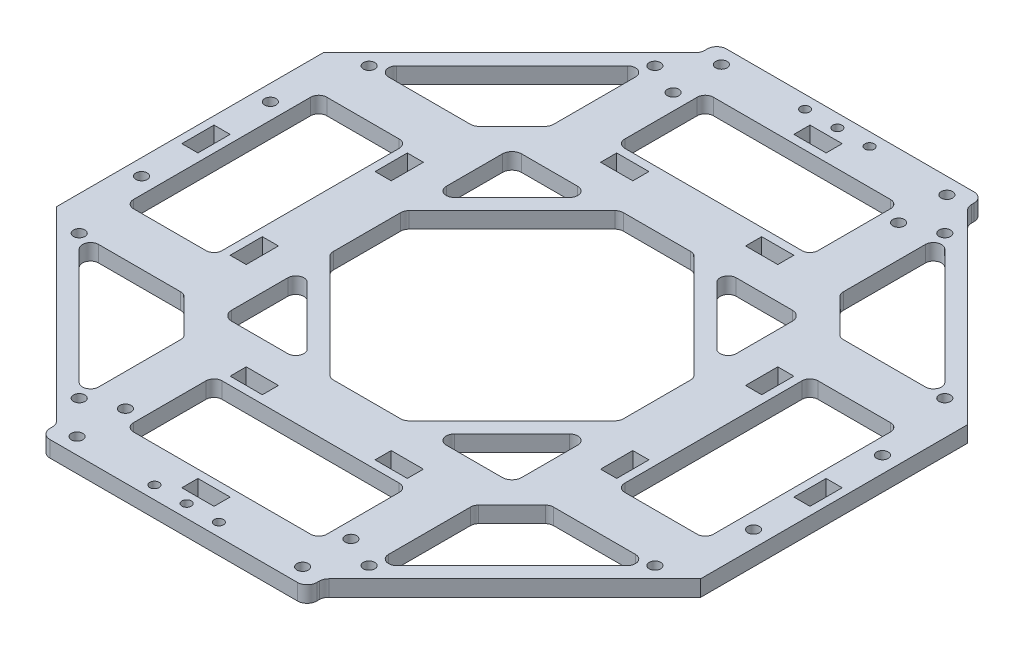
SolidWorks part; units mm, degrees
material "Custom Plastic"
ref_plane "Front Plane" through (0, 0, 0) normal (0, 0, 1) x (1, 0, 0)
ref_plane "Top Plane" through (0, 0, 0) normal (0, 1, 0) x (1, 0, 0)
ref_plane "Right Plane" through (0, 0, 0) normal (1, 0, 0) x (0, 0, -1)
ref_axis "Axis1" through (0, -18.6023, 0) along (0, 1, 0)
sketch "Base sketch" plane through (0, 0, 0) normal (0, 1, 0) x (1, 0, 0)
  line L1 (-127, 52.6051) -> (-127, -52.6051)
  line L2 (-127, -52.6051) -> (-52.6051, -127)
  line L3 (-52.6051, -127) -> (52.6051, -127)
  line L4 (52.6051, -127) -> (127, -52.6051)
  line L5 (127, -52.6051) -> (127, 52.6051)
  line L6 (127, 52.6051) -> (52.6051, 127)
  line L7 (52.6051, 127) -> (-52.6051, 127)
  line L8 (-52.6051, 127) -> (-127, 52.6051)
  circle A0 centre (0, 0) radius 127 construction
  dimension "D1" = 254
extrude "Base" add sketch "Base sketch" along normal blind 6.35
sketch "Sketch3" plane through (0, 6.35, 0) normal (0, 1, 0) x (1, 0, 0)
  line L0 (52.6051, 127) -> (-52.6051, 127) construction
  line L1 (-38.1, 114.3) -> (38.1, 114.3)
  line L2 (-38.1, 114.3) -> (-38.1, 79.375)
  line L4 (-38.1, 79.375) -> (38.1, 79.375)
  line L5 (38.1, 114.3) -> (38.1, 79.375)
  point P6 (0, 79.375)
  dimension "D1" = 76.2
  dimension "D2" = 34.925
  dimension "D3" = 12.7
extrude "Wheel cutout" cut sketch "Sketch3" against normal up to next
fillet "Wheel cutout fillets" radius 3.175 4 edges at (38.1, 3.175, -114.3) (38.1, 3.175, -79.375) (-38.1, 3.175, -79.375) (-38.1, 3.175, -114.3)
pattern_circular "Wheel cutout pattern" count 4 over 360 about axis through (0, -18.6023, 0) along (0, 1, 0) of "Wheel cutout", "Wheel cutout fillets"
sketch "Sketch4" plane through (0, 6.35, 0) normal (0, 1, 0) x (1, 0, 0)
  line L0 (0, 0) -> (0, 127) construction
  line L1 (52.6051, 127) -> (-52.6051, 127) construction
  line L2 (34.925, 120.65) -> (-34.925, 120.65) construction
  line L3 (-34.925, 123.825) -> (-22.225, 123.825) construction
  line L4 (-34.925, 123.825) -> (-34.925, 117.475) construction
  line L5 (-34.925, 117.475) -> (-22.225, 117.475) construction
  line L6 (-22.225, 123.825) -> (-22.225, 117.475) construction
  line L7 (-34.925, 123.825) -> (-22.225, 117.475) construction
  line L8 (-34.925, 117.475) -> (-22.225, 123.825) construction
  line L9 (34.925, 114.3) -> (-34.925, 114.3) construction
  line L10 (34.925, 117.475) -> (22.225, 123.825) construction
  line L11 (34.925, 123.825) -> (22.225, 117.475) construction
  line L12 (22.225, 123.825) -> (22.225, 117.475) construction
  line L13 (34.925, 117.475) -> (22.225, 117.475) construction
  line L14 (34.925, 123.825) -> (34.925, 117.475) construction
  line L15 (34.925, 123.825) -> (22.225, 123.825) construction
  line L16 (-38.1, 96.8375) -> (38.1, 96.8375) construction
  line L17 (-38.1, 111.125) -> (-38.1, 82.55) construction
  line L18 (38.1, 82.55) -> (38.1, 111.125) construction
  line L19 (34.925, 69.85) -> (22.225, 76.2) construction
  line L20 (34.925, 76.2) -> (22.225, 69.85) construction
  line L21 (-34.925, 76.2) -> (-22.225, 69.85) construction
  line L22 (-34.925, 69.85) -> (-22.225, 76.2) construction
  line L23 (34.925, 73.025) -> (-34.925, 73.025) construction
  line L24 (34.925, 69.85) -> (22.225, 69.85)
  line L25 (34.925, 69.85) -> (34.925, 76.2)
  line L26 (34.925, 76.2) -> (22.225, 76.2)
  line L27 (22.225, 69.85) -> (22.225, 76.2)
  line L28 (-22.225, 69.85) -> (-22.225, 76.2)
  line L29 (-34.925, 76.2) -> (-22.225, 76.2)
  line L30 (-34.925, 69.85) -> (-34.925, 76.2)
  line L31 (-34.925, 69.85) -> (-22.225, 69.85)
  line L33 (-6.35, 117.475) -> (6.35, 117.475)
  line L34 (-6.35, 117.475) -> (-6.35, 123.825)
  line L35 (-6.35, 123.825) -> (6.35, 123.825)
  line L36 (6.35, 117.475) -> (6.35, 123.825)
  line L37 (-6.35, 117.475) -> (6.35, 123.825) construction
  line L38 (-6.35, 123.825) -> (6.35, 117.475) construction
  point P5 (-28.575, 120.65)
  point P12 (0, 120.65)
  point P17 (28.575, 120.65)
  point P34 (28.575, 73.025)
  point P35 (-28.575, 73.025)
  point P38 (0, 120.65)
  dimension "D1" = 6.35
  dimension "D2" = 12.7
  dimension "D3" = 69.85
  dimension "D4" = 6.35
  dimension "D5" = 12.7
  dimension "D6" = 6.35
extrude "Support cutouts" cut sketch "Sketch4" against normal up to next
pattern_circular "Support cutout pattern" count 4 over 360 about axis through (0, -18.6023, 0) along (0, 1, 0) of "Support cutouts"
sketch "Sketch5" plane through (0, 6.35, 0) normal (0, 1, 0) x (1, 0, 0)
  line L0 (13.2899, 57.15) -> (-13.2899, 57.15)
  line L1 (-15.5349, 56.2201) -> (-35.8775, 35.8775)
  line L2 (0, 0) -> (0, 57.15) construction
  line L3 (35.8775, 35.8775) -> (15.5349, 56.2201)
  line L4 (0, 0) -> (-89.8026, 89.8026) construction
  line L5 (127, 52.6051) -> (52.6051, 127) construction
  line L6 (89.8026, 89.8026) -> (0, 0) construction
  line L7 (-52.6051, 127) -> (-127, 52.6051) construction
  line L8 (22.225, 69.85) -> (34.925, 69.85) construction
  line L9 (-35.8775, 35.8775) -> (0, 0)
  line L10 (0, 0) -> (35.8775, 35.8775)
  line L11 (-31.2504, 57.15) -> (-57.15, 57.15)
  line L12 (-57.15, 57.15) -> (-40.3676, 40.3676)
  line L13 (-40.3676, 40.3676) -> (-29.0053, 51.7299)
  line L14 (31.2504, 57.15) -> (57.15, 57.15)
  line L15 (57.15, 57.15) -> (40.3676, 40.3676)
  line L16 (40.3676, 40.3676) -> (29.0053, 51.7299)
  arc A0 (13.2899, 57.15) -> (15.5349, 56.2201) centre (13.2899, 53.975) cw
  arc A1 (34.925, 79.375) -> (38.1, 82.55) centre (34.925, 82.55) ccw construction
  arc A4 (-13.2899, 57.15) -> (-15.5349, 56.2201) centre (-13.2899, 53.975) ccw
  arc A8 (31.2504, 57.15) -> (29.0053, 51.7299) centre (31.2504, 53.975) ccw
  arc A9 (-31.2504, 57.15) -> (-29.0053, 51.7299) centre (-31.2504, 53.975) cw
  point P19 (14.605, 57.15)
  point P29 (-14.605, 57.15)
  point P37 (57.15, 57.15)
  point P40 (40.3676, 40.3676)
  point P47 (-40.3676, 40.3676)
  point P50 (-57.15, 57.15)
  dimension "D4" = 6.35
  dimension "D1" = 12.7
  dimension "D2" = 29.21
  dimension "D3" = 6.35
extrude "Motor Clearance" cut sketch "Sketch5" against normal through all
pattern_circular "CirPattern1" count 4 every 90 about axis through (0, -18.6023, 0) along (0, 1, 0) of "Motor Clearance"
sketch "Aligner" [suppressed] plane through (0, 6.35, 0) normal (0, 1, 0) x (1, 0, 0)
  line L0 (74.1687, 87.0459) -> (70.2318, 109.3733)
  line L1 (127, 52.6051) -> (52.6051, 127) construction
  line L2 (70.2318, 109.3733) -> (109.3733, 70.2318)
  line L3 (127, 44.45) -> (109.3733, 70.2318)
  line L4 (89.8026, 89.8026) -> (0, 0) construction
  line L5 (87.0459, 74.1687) -> (109.3733, 70.2318)
  line L6 (70.2318, 109.3733) -> (67.4939, 124.9011)
  line L7 (64.9924, 127) -> (44.45, 127)
  line L9 (109.3733, 70.2318) -> (124.9011, 67.4939)
  line L10 (127, 64.9924) -> (127, 44.45)
  line L11 (52.6051, 127) -> (-52.6051, 127) construction
  line L12 (44.45, 127) -> (70.2318, 109.3733)
  line L13 (38.1, 82.55) -> (38.1, 111.125) construction
  arc A0 (74.1687, 87.0459) -> (87.0459, 74.1687) centre (89.8026, 89.8026) ccw
  arc A1 (124.9011, 67.4939) -> (127, 64.9924) centre (124.46, 64.9924) cw
  arc A2 (67.4939, 124.9011) -> (64.9924, 127) centre (64.9924, 124.46) ccw
  dimension "D1" = 15.875
  dimension "D2" = 2.54
  dimension "D3" = 55
  dimension "D5" = 6.35
sketch "Aligner Lightenning hole skt" plane through (0, 6.35, 0) normal (0, 1, 0) x (1, 0, 0)
  line L0 (-108.0548, 62.5701) -> (-62.5701, 108.0548)
  line L1 (-57.15, 105.8097) -> (-57.15, 73.4808)
  line L2 (-58.0799, 71.2358) -> (-71.2358, 58.0799)
  line L3 (-73.4808, 57.15) -> (-105.8097, 57.15)
  line L4 (-52.6051, 127) -> (-127, 52.6051) construction
  line L5 (0, 0) -> (-64.6578, 64.6578) construction
  line L6 (-64.6578, 64.6578) -> (-85.3124, 85.3124) construction
  line L7 (-85.3124, 85.3124) -> (-89.8026, 89.8026) construction
  line L8 (-82.55, 38.1) -> (-111.125, 38.1) construction
  arc A1 (-108.0548, 62.5701) -> (-105.8097, 57.15) centre (-105.8097, 60.325) ccw
  arc A2 (-71.2358, 58.0799) -> (-73.4808, 57.15) centre (-73.4808, 60.325) cw
  arc A3 (-57.15, 73.4808) -> (-58.0799, 71.2358) centre (-60.325, 73.4808) cw
  arc A4 (-62.5701, 108.0548) -> (-57.15, 105.8097) centre (-60.325, 105.8097) cw
  dimension "D4" = 3.175
  dimension "D1" = 6.35
  dimension "D2" = 19.05
  dimension "D3" = 29.21
extrude "Aligher Lightenning holes" cut sketch "Aligner Lightenning hole skt" against normal through all
pattern_circular "CirPattern3" count 4 over 360 about axis through (0, -18.6023, 0) along (0, 1, 0) of "Aligher Lightenning holes"
sketch "Sketch9" plane through (0, 6.35, 0) normal (0, 1, 0) x (1, 0, 0)
  line L0 (-127, 0) -> (127, 0) construction
  line L1 (-52.6051, -127) -> (52.6051, -127)
  line L2 (-52.6051, -127) -> (-52.6051, -133.35)
  line L3 (-52.6051, -133.35) -> (52.6051, -133.35)
  line L4 (52.6051, -127) -> (52.6051, -133.35)
  line L5 (127, -52.6051) -> (127, 52.6051) construction
  line L6 (-127, 52.6051) -> (-127, -52.6051) construction
  line L7 (52.6051, 127) -> (52.6051, 133.35)
  line L8 (-52.6051, 133.35) -> (52.6051, 133.35)
  line L9 (-52.6051, 127) -> (-52.6051, 133.35)
  line L10 (-52.6051, 127) -> (52.6051, 127)
  dimension "D1" = 6.35
extrude "Extend for line sensor mount" add sketch "Sketch9" against normal through all contours L1 L4 L3 L2 | L10 L7 L8 L9
sketch "Aligner hole sketch" plane through (0, 6.35, 0) normal (0, 1, 0) x (1, 0, 0)
  line L0 (0, -133.35) -> (0, 0) construction
  line L1 (-44.45, -107.95) -> (-44.45, -127) construction
  line L2 (44.45, -107.95) -> (0, -107.95) construction
  line L3 (0, -107.95) -> (-44.45, -107.95) construction
  line L4 (-44.45, -127) -> (0, -127) construction
  line L5 (0, -127) -> (44.45, -127) construction
  line L6 (44.45, -127) -> (44.45, -107.95) construction
  line L8 (-52.6051, -133.35) -> (52.6051, -133.35) construction
  circle A1 centre (-44.45, -127) radius 2.2479
  circle A2 centre (-44.45, -107.95) radius 2.2479
  circle A3 centre (44.45, -107.95) radius 2.2479
  circle A4 centre (44.45, -127) radius 2.2479
  dimension "D3" = 4.4958
  dimension "D1" = 19.05
  dimension "D2" = 6.35
  dimension "D4" = 44.45
extrude "Aligner holes" cut sketch "Aligner hole sketch" against normal through all
fillet "Fillet1" radius 3.81 12 edges at (52.6051, 3.175, -133.35) (-52.6051, 3.175, -133.35) (52.6051, 3.175, 133.35) (-52.6051, 3.175, 133.35) (52.6051, 3.175, -127) (-52.6051, 3.175, -127) (-52.6051, 3.175, 127) (52.6051, 3.175, 127) (-57.15, 3.175, 57.15) (57.15, 3.175, 57.15) (57.15, 3.175, -57.15) (-57.15, 3.175, -57.15)
sketch "Sketch12" plane through (0, 6.35, 0) normal (0, 1, 0) x (1, 0, 0)
  line L0 (-57.15, -113.4749) -> (0, -113.4749) construction
  line L1 (0, -113.4749) -> (57.15, -113.4749) construction
  line L2 (0, -113.4749) -> (0, 0) construction
  line L3 (57.15, -73.4808) -> (57.15, -105.8097) construction
  line L4 (-57.15, -105.8097) -> (-57.15, -73.4808) construction
  line L5 (-108.0548, -62.5701) -> (-62.5701, -108.0548) construction
  line L6 (62.5701, -108.0548) -> (108.0548, -62.5701) construction
  circle A2 centre (-57.15, -113.4749) radius 2.2479
  circle A3 centre (57.15, -113.4749) radius 2.2479
  circle A4 centre (44.45, -107.95) radius 2.2479 construction
extrude "Cut-Extrude2" cut sketch "Sketch12" against normal through all
pattern_circular "CirPattern5" count 4 every 90 about axis through (0, -18.6023, 0) along (0, 1, 0) of "Cut-Extrude2"
pattern_circular "CirPattern6" count 2 every 180 about axis through (0, -18.6023, 0) along (0, 1, 0) of "Aligner holes"
sketch "light sensor mount" plane through (0, 6.35, 0) normal (0, 1, 0) x (1, 0, 0)
  line L1 (-12.7, -128.27) -> (0, -128.27) construction
  line L2 (0, -128.27) -> (12.7, -128.27) construction
  line L3 (0, -128.27) -> (0, 128.27) construction
  line L5 (-48.7951, -133.35) -> (48.7951, -133.35) construction
  line L8 (-120.65, 0) -> (120.65, 0) construction
  line L12 (0, 128.27) -> (12.7, 128.27) construction
  line L13 (-12.7, 128.27) -> (0, 128.27) construction
  line L14 (-120.65, 25.4) -> (-120.65, 0) construction
  line L15 (-120.65, 0) -> (-120.65, -25.4) construction
  line L16 (-127, 52.6051) -> (-127, -52.6051) construction
  line L17 (120.65, 0) -> (120.65, -25.4) construction
  line L18 (120.65, 25.4) -> (120.65, 0) construction
  circle A0 centre (-120.65, 25.4) radius 2.2479
  circle A1 centre (-120.65, -25.4) radius 2.2479
  circle A2 centre (120.65, 25.4) radius 2.2479
  circle A3 centre (120.65, -25.4) radius 2.2479
  circle A5 centre (-113.4749, 57.15) radius 2.2479 construction
  point P15 (0, 0)
  point P20 (0, 0)
  dimension "D2" = 5.08
  dimension "D1" = 12.7
  dimension "D3" = 25.4
  dimension "D4" = 6.35
hole_wizard "light sensor mount holes" positions "Sketch16" profile "Sketch15" hole size "#6" standard "ANSI Inch" end condition through all
sketch "Sketch16" plane through (0, 6.35, 0) normal (0, 1, 0) x (1, 0, 0)
  point P0 (-12.7, -128.27)
  point P3 (0, -128.27)
  point P6 (12.7, -128.27)
  point P16 (-12.7, 128.27)
  point P19 (0, 128.27)
  point P22 (12.7, 128.27)
sketch "Sketch15" plane through (-12.7, 6.35, 128.27) normal (1, 0, 0) x (0, 0, 1)
  line L0 (0, 0) -> (0, 6.35)
  line L1 (0, 6.35) -> (1.8288, 6.35)
  line L2 (1.8288, 6.35) -> (1.8288, 0)
  line L5 (1.8288, 0) -> (0, 0)
  line L11 (0, -6.35) -> (0, 107.95) construction
  dimension "Thru Hole Dia." = 3.6576
  dimension "Thru Hole Depth" = 6.35
pattern_circular "CirPattern7" count 2 every 180 about axis through (0, -18.6023, 0) along (0, 1, 0) of "light sensor mount holes"
extrude "Cut-Extrude3" cut sketch "light sensor mount" against normal through all
equation "\"MAT_THICKNESS\"=0.25"
equation "\"D1@Sketch4\"=\"MAT_THICKNESS\""
equation "\"D1@Base\"=\"MAT_THICKNESS\""
equation "\"D6@Sketch4\"=\"MAT_THICKNESS\""
equation "\"D3@Sketch4\"=2.75"
